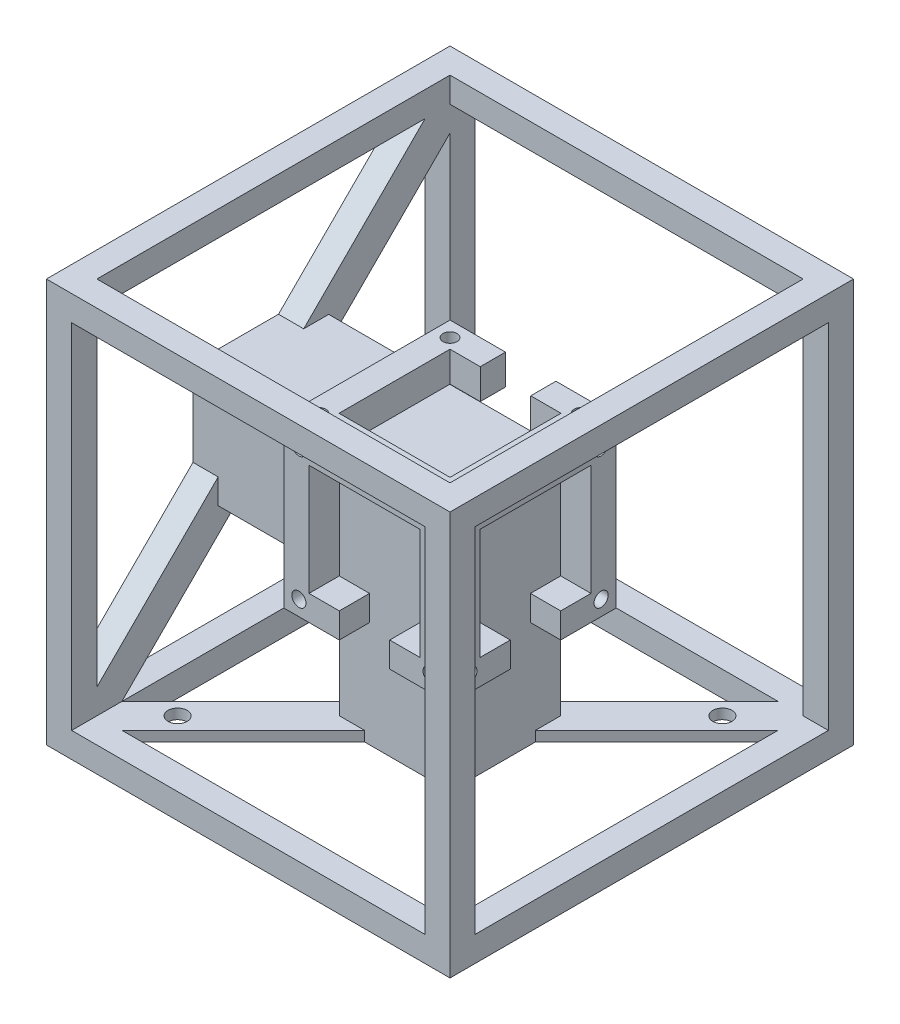
SolidWorks part; units mm, degrees
ref_plane "前视基准面" through (0, 0, 0) normal (0, 0, 1) x (1, 0, 0)
ref_plane "上视基准面" through (0, 0, 0) normal (0, 1, 0) x (1, 0, 0)
ref_plane "右视基准面" through (0, 0, 0) normal (1, 0, 0) x (0, 0, -1)
other "Configuration Table"
sketch "草图1" plane through (0, 0, 0) normal (0, 1, 0) x (1, 0, 0)
  line L0 (75, 75) -> (5, 5) construction
  line L1 (0, 0) -> (80, 0)
  line L2 (0, 0) -> (0, 80)
  line L3 (0, 80) -> (80, 80)
  line L4 (80, 0) -> (80, 80)
  line L5 (5, 5) -> (75, 5) construction
  line L6 (5, 5) -> (5, 75) construction
  line L7 (5, 75) -> (75, 75) construction
  line L8 (75, 5) -> (75, 75) construction
  line L9 (5, 75) -> (75, 5) construction
  line L10 (5, 9.9497) -> (29.0503, 34)
  line L11 (5, 70.0503) -> (29.0503, 46)
  line L12 (9.9497, 5) -> (34, 29.0503)
  line L13 (9.9497, 75) -> (34, 50.9497)
  line L14 (5, 40) -> (75, 40) construction
  line L15 (40, 5) -> (40, 75) construction
  line L16 (5, 70.0503) -> (5, 9.9497)
  line L17 (70.0503, 5) -> (9.9497, 5)
  line L18 (75, 9.9497) -> (75, 70.0503)
  line L19 (70.0503, 75) -> (9.9497, 75)
  line L20 (46, 29.0503) -> (70.0503, 5)
  line L21 (46, 50.9497) -> (70.0503, 75)
  line L22 (50.9497, 34) -> (75, 9.9497)
  line L23 (50.9497, 46) -> (75, 70.0503)
  line L24 (29.0503, 46) -> (29.0503, 34)
  line L29 (34, 50.9497) -> (46, 50.9497)
  line L30 (50.9497, 46) -> (50.9497, 34)
  line L31 (34, 29.0503) -> (46, 29.0503)
  line L33 (75, 5) -> (75, 0) construction
  circle A0 centre (13, 13) radius 1.9
  circle A1 centre (67, 13) radius 1.9
  circle A2 centre (67, 67) radius 1.9
  circle A3 centre (13, 67) radius 1.9
  point P9 (40, 0)
  dimension "D9" = 3.8
  dimension "D1" = 80
  dimension "D2" = 80
  dimension "D3" = 5
  dimension "D4" = 5
  dimension "D5" = 5
  dimension "D6" = 5
  dimension "D7" = 12
  dimension "D8" = 7
  dimension "D10" = 54
  dimension "D11" = 12
  dimension "D12" = 12
  dimension "D13" = 12
  dimension "D14" = 7
extrude "凸台-拉伸1" add sketch "草图1" along normal blind 5
sketch "草图6" plane through (0, 0, 0) normal (0, -1, 0) x (1, 0, 0)
  line L0 (75, -9.9497) -> (75, -70.0503) construction
  line L1 (5, -5) -> (75, -5)
  line L2 (5, -5) -> (5, -75)
  line L3 (5, -75) -> (75, -75)
  line L4 (0, 0) -> (0, -80)
  line L5 (0, -80) -> (80, -80)
  line L6 (80, -80) -> (80, 0)
  line L7 (80, 0) -> (0, 0)
  line L8 (0, 0) -> (0, -80)
  line L9 (0, -80) -> (80, -80)
  line L10 (80, -80) -> (80, 0)
  line L11 (80, 0) -> (0, 0)
  line L12 (75, -5) -> (75, -75)
  line L13 (70.0503, -75) -> (9.9497, -75) construction
  line L14 (5, -70.0503) -> (5, -9.9497) construction
  line L15 (9.9497, -5) -> (70.0503, -5) construction
  circle M9 centre (67, -67) radius 1.9
  circle M10 centre (13, -13) radius 1.9
  line M15 (29.0503, -46) -> (5, -70.0503)
  line M17 (5, -9.9497) -> (29.0503, -34)
  line M18 (9.9497, -75) -> (34, -50.9497)
  line M19 (46, -50.9497) -> (70.0503, -75)
  line M22 (70.0503, -5) -> (46, -29.0503)
  line M23 (34, -29.0503) -> (9.9497, -5)
  line M25 (75, -70.0503) -> (50.9497, -46)
  line M26 (50.9497, -34) -> (75, -9.9497)
  circle M27 centre (67, -13) radius 1.9
  circle M28 centre (13, -67) radius 1.9
  dimension "D1" = 0
extrude "切除-拉伸1" cut sketch "草图6" against normal blind 3 contours L12 L1 L2 L3 M22 M23 M17 M15 M18 M19 M25 M26 M10 M27 M28 M9 region at (40, 0, -40)
sketch "草图4" plane through (0, 5, 0) normal (0, 1, 0) x (1, 0, 0)
  line L1 (0, 80) -> (5, 80)
  line L2 (0, 80) -> (0, 75)
  line L3 (0, 75) -> (5, 75)
  line L4 (0, 80) -> (0, 0)
  line L5 (0, 0) -> (80, 0)
  line L6 (80, 0) -> (80, 80)
  line L7 (80, 80) -> (0, 80)
  line L8 (0, 80) -> (0, 0)
  line L9 (0, 0) -> (80, 0)
  line L10 (80, 0) -> (80, 80)
  line L11 (80, 80) -> (0, 80)
  line L12 (5, 80) -> (5, 75)
  line L13 (80, 80) -> (75, 80)
  line L14 (80, 80) -> (80, 75)
  line L15 (80, 75) -> (75, 75)
  line L16 (75, 80) -> (75, 75)
  line L17 (80, 0) -> (75, 0)
  line L18 (80, 0) -> (80, 5)
  line L19 (80, 5) -> (75, 5)
  line L20 (75, 0) -> (75, 5)
  line L21 (0, 0) -> (5, 0)
  line L22 (0, 0) -> (0, 5)
  line L23 (0, 5) -> (5, 5)
  line L24 (5, 0) -> (5, 5)
  line M24 (0, 0) -> (80, 0)
  line M25 (80, 0) -> (80, 80)
  line M26 (80, 80) -> (0, 80)
  dimension "D2" = 5
  dimension "D3" = 5
  dimension "D4" = 5
  dimension "D5" = 5
  dimension "D6" = 5
  dimension "D7" = 5
  dimension "D8" = 5
  dimension "D9" = 5
  dimension "D1" = 0
extrude "凸台-拉伸2" add sketch "草图4" along normal blind 70 contours L24 L23 L8 M24 | L20 L9 L19 M25 | L16 L15 L10 M26 | L1 L12 L3 L2 region at (77.5, 5, -77.5) region at (2.5, 5, -2.5) region at (77.5, 5, -2.5)
sketch "草图5" plane through (0, 75, 0) normal (0, 1, 0) x (1, 0, 0)
  line L1 (0, 80) -> (80, 80)
  line L2 (0, 80) -> (0, 0)
  line L3 (0, 0) -> (80, 0)
  line L4 (80, 80) -> (80, 0)
  line L5 (5, 75) -> (75, 75)
  line L6 (5, 75) -> (5, 5)
  line L7 (5, 5) -> (75, 5)
  line L8 (75, 75) -> (75, 5)
  line L12 (75, 80) -> (5, 80)
  line L13 (5, 80) -> (5, 75)
  line L14 (5, 75) -> (0, 75)
  line L15 (0, 75) -> (0, 5)
  line L16 (0, 5) -> (5, 5)
  line L17 (5, 5) -> (5, 0)
  line L18 (5, 0) -> (75, 0)
  line L19 (75, 0) -> (75, 5)
  line L20 (75, 5) -> (80, 5)
  line L21 (80, 5) -> (80, 75)
  line L22 (80, 75) -> (75, 75)
  line L23 (75, 75) -> (75, 80)
  line L24 (75, 80) -> (5, 80)
  line L27 (0, 75) -> (0, 5)
  line L30 (5, 0) -> (75, 0)
  line L33 (80, 5) -> (80, 75)
  line M17 (0, 0) -> (5, 0)
  line M18 (5, 0) -> (5, 5)
  line M19 (5, 5) -> (0, 5)
  line M20 (0, 5) -> (0, 0)
  dimension "D1" = 0
extrude "凸台-拉伸3" add sketch "草图5" along normal blind 5 contours L5 L8 L7 L3 L4 L1 L2 L6 M18 M19 | M20 M17 M18 M19 region at (2.5, 75, -77.5) region at (40, 75, -77.5) region at (2.5, 75, -40) region at (77.5, 75, -77.5) region at (2.5, 75, -2.5) region at (77.5, 75, -40) region at (40, 75, -2.5) region at (77.5, 75, -2.5)
sketch "草图7" plane through (5, 0, 0) normal (1, 0, 0) x (0, 0, -1)
  line L1 (29.0503, 46) -> (29.0503, 34)
  line L5 (75, 5) -> (5, 75) construction
  line L6 (5, 5) -> (75, 75) construction
  line L7 (5, 70.0503) -> (29.0503, 46)
  line L8 (5, 75) -> (5, 5) construction
  line L9 (70.0503, 5) -> (9.9497, 5) construction
  line L10 (9.9497, 5) -> (34, 29.0503)
  line L11 (75, 75) -> (75, 5) construction
  line L12 (9.9497, 75) -> (34, 50.9497)
  line L13 (5, 9.9497) -> (29.0503, 34)
  line L14 (46, 50.9497) -> (70.0503, 75)
  line L15 (50.9497, 34) -> (75, 9.9497)
  line L16 (50.9497, 46) -> (75, 70.0503)
  line L17 (46, 29.0503) -> (70.0503, 5)
  line L18 (34, 29.0503) -> (46, 29.0503)
  line L19 (50.9497, 34) -> (50.9497, 46)
  line L20 (46, 50.9497) -> (34, 50.9497)
  line L21 (75, 5) -> (70.0503, 5)
  line L22 (75, 9.9497) -> (75, 5)
  line L23 (5, 9.9497) -> (5, 5)
  line L24 (5, 5) -> (9.9497, 5)
  line L25 (5, 70.0503) -> (5, 75)
  line L26 (5, 75) -> (9.9497, 75)
  line L27 (70.0503, 75) -> (75, 75)
  line L28 (75, 75) -> (75, 70.0503)
  dimension "D1" = 7
  dimension "D2" = 7
  dimension "D3" = 12
  dimension "D4" = 12
  dimension "D5" = 12
  dimension "D6" = 12
extrude "凸台-拉伸5" add sketch "草图7" against normal up to surface (5 mm away) up to face at (0, 40, -40)
sketch "草图8" plane through (0, 80, 0) normal (0, 1, 0) x (1, 0, 0)
  line L0 (75, 75) -> (75, 5) construction
  line L1 (5, 75) -> (5, 5) construction
  line L2 (5, 75) -> (75, 75) construction
  circle A0 centre (40, 40) radius 35
sketch "草图9" plane through (0, 0, 0) normal (0, 0, 1) x (1, 0, 0)
  line L0 (75, 75) -> (75, 5) construction
  line L1 (5, 75) -> (5, 5) construction
  line L2 (5, 75) -> (75, 75) construction
  circle A0 centre (40, 40) radius 35
sketch "草图10" plane through (80, 0, 0) normal (1, 0, 0) x (0, 0, -1)
  line L0 (75, 75) -> (75, 5) construction
  line L1 (5, 75) -> (5, 5) construction
  line L2 (75, 75) -> (5, 75) construction
  circle A0 centre (40, 40) radius 35
sketch "草图11" plane through (5, 0, 0) normal (1, 0, 0) x (0, 0, -1)
  line L0 (50.9497, 34) -> (50.9497, 46) construction
  line L1 (29.0503, 50.9497) -> (50.9497, 50.9497)
  line L2 (29.0503, 50.9497) -> (29.0503, 29.0503)
  line L3 (29.0503, 29.0503) -> (50.9497, 29.0503)
  line L4 (50.9497, 50.9497) -> (50.9497, 29.0503)
  line L5 (46, 50.9497) -> (34, 50.9497) construction
  line L6 (29.0503, 46) -> (29.0503, 34) construction
  line L7 (34, 29.0503) -> (46, 29.0503) construction
extrude "凸台-拉伸6" add sketch "草图11" along normal up to surface (45.9497 mm away) up to face at (50.9497, 4, -40)
sketch "草图12" plane through (0, 5, 0) normal (0, 1, 0) x (1, 0, 0)
  line L0 (46, 29.0503) -> (34, 29.0503) construction
  line L1 (29.0503, 29.0503) -> (50.9497, 29.0503)
  line L2 (29.0503, 29.0503) -> (29.0503, 50.9497)
  line L3 (29.0503, 50.9497) -> (50.9497, 50.9497)
  line L4 (50.9497, 29.0503) -> (50.9497, 50.9497)
  line L5 (50.9497, 46) -> (50.9497, 34) construction
  line L6 (34, 50.9497) -> (46, 50.9497) construction
  line L7 (29.0503, 34) -> (29.0503, 46) construction
extrude "凸台-拉伸7" add sketch "草图12" along normal up to surface (45.9497 mm away) up to face at (15.2374, 50.9497, -40)
sketch "草图16" plane through (0, 0, -29.0503) normal (0, 0, 1) x (1, 0, 0)
  line L1 (24, 56) -> (56, 56)
  line L2 (24, 56) -> (24, 24)
  line L3 (24, 24) -> (56, 24)
  line L4 (56, 56) -> (56, 24)
  line L5 (29, 51) -> (51, 51)
  line L6 (29, 51) -> (29, 29)
  line L7 (29, 29) -> (51, 29)
  line L8 (51, 51) -> (51, 29)
  dimension "D1" = 32
  dimension "D2" = 32
  dimension "D3" = 16
  dimension "D4" = 16
  dimension "D5" = 5
  dimension "D6" = 5
  dimension "D7" = 5
  dimension "D8" = 5
extrude "凸台-拉伸9" add sketch "草图16" along normal blind 6
sketch "草图18" plane through (50.9497, 0, 0) normal (1, 0, 0) x (0, 0, -1)
  line L1 (24, 56) -> (56, 56)
  line L2 (24, 56) -> (24, 24)
  line L3 (24, 24) -> (56, 24)
  line L4 (56, 56) -> (56, 24)
  line L5 (29, 51) -> (51, 51)
  line L6 (29, 51) -> (29, 29)
  line L7 (29, 29) -> (51, 29)
  line L8 (51, 51) -> (51, 29)
  dimension "D1" = 32
  dimension "D2" = 32
  dimension "D3" = 16
  dimension "D4" = 16
  dimension "D5" = 5
  dimension "D6" = 5
  dimension "D7" = 5
  dimension "D8" = 5
extrude "凸台-拉伸10" add sketch "草图18" along normal blind 6
sketch "草图19" plane through (0, 50.9497, 0) normal (0, 1, 0) x (1, 0, 0)
  line L1 (24, 56) -> (56, 56)
  line L2 (24, 56) -> (24, 24)
  line L3 (24, 24) -> (56, 24)
  line L4 (56, 56) -> (56, 24)
  line L5 (29, 51) -> (51, 51)
  line L6 (29, 51) -> (29, 29)
  line L7 (29, 29) -> (51, 29)
  line L8 (51, 51) -> (51, 29)
  dimension "D1" = 5
  dimension "D2" = 5
  dimension "D3" = 5
  dimension "D4" = 5
  dimension "D5" = 16
  dimension "D6" = 16
  dimension "D7" = 32
  dimension "D8" = 32
extrude "凸台-拉伸11" add sketch "草图19" along normal blind 6
sketch "草图20" plane through (0, 0, -23.0503) normal (0, 0, 1) x (1, 0, 0)
  line L0 (40, 40) -> (56, 40) construction
  line L2 (40, 40) -> (40, 23.6995) construction
  line L6 (29, 51) -> (29, 29) construction
  line L8 (24, 56) -> (24, 24) construction
  line L11 (45, 29) -> (35, 29)
  line L12 (29.0503, 29) -> (50.9497, 29) construction
  line L13 (29, 29) -> (51, 29) construction
  line L14 (35, 29) -> (35, 24)
  line L15 (24, 24) -> (56, 24) construction
  line L16 (35, 24) -> (45, 24)
  line L17 (45, 29) -> (45, 24)
  circle A0 centre (53, 27) radius 1.4
  circle A1 centre (27, 27) radius 1.4
  circle A2 centre (53, 53) radius 1.4
  circle A3 centre (27, 53) radius 1.4
  point P21 (29, 40)
  point P22 (24, 40)
  point P29 (40, 24)
  point P30 (40, 29)
  dimension "D1" = 2.8
  dimension "D2" = 26
  dimension "D3" = 26
  dimension "D4" = 5
extrude "切除-拉伸2" cut sketch "草图20" against normal up to surface (6 mm away) and the other way blind 2 up to face at (53.5, 39.9749, -29.0503)
sketch "草图21" plane through (56.9497, 0, 0) normal (1, 0, 0) x (0, 0, -1)
  line L0 (40, 40) -> (46.9642, 40) construction
  line L1 (40, 40) -> (40, 33.1563) construction
  line L2 (45, 29) -> (35, 29)
  line L3 (29, 29) -> (51, 29) construction
  line L4 (35, 29) -> (35, 24)
  line L5 (24, 24) -> (56, 24) construction
  line L6 (35, 24) -> (45, 24)
  line L7 (45, 29) -> (45, 24)
  circle A0 centre (53, 27) radius 1.4
  circle A1 centre (27, 27) radius 1.4
  circle A2 centre (27, 53) radius 1.4
  circle A3 centre (53, 53) radius 1.4
  point P21 (40, 24)
  point P22 (40, 29)
  dimension "D1" = 2.8
  dimension "D2" = 26
  dimension "D3" = 26
  dimension "D4" = 5
extrude "切除-拉伸3" cut sketch "草图21" against normal up to surface (6 mm away) and the other way blind 2 up to face at (50.9497, 39.9749, -26.5)
sketch "草图23" plane through (0, 56.9497, 0) normal (0, 1, 0) x (1, 0, 0)
  line L0 (40, 40) -> (46.9412, 40) construction
  line L1 (40, 40) -> (40, 48.2952) construction
  line L2 (35, 51) -> (45, 51)
  line L3 (51, 51) -> (29, 51) construction
  line L4 (45, 51) -> (45, 56)
  line L5 (56, 56) -> (24, 56) construction
  line L6 (45, 56) -> (35, 56)
  line L7 (35, 51) -> (35, 56)
  circle A0 centre (27, 53) radius 1.4
  circle A1 centre (53, 53) radius 1.4
  circle A2 centre (53, 27) radius 1.4
  circle A3 centre (27, 27) radius 1.4
  point P16 (0, 0)
  point P21 (0, 0)
  point P22 (0, 0)
  point P23 (39.9749, 51.4039)
  point P24 (0, 0)
  point P26 (40, 56)
  point P27 (40, 51)
  dimension "D1" = 2.8
  dimension "D2" = 26
  dimension "D3" = 26
  dimension "D4" = 5
extrude "切除-拉伸4" cut sketch "草图23" against normal up to surface (6 mm away) and the other way blind 2 up to face at (34.6499, 50.9497, -52.6499)
